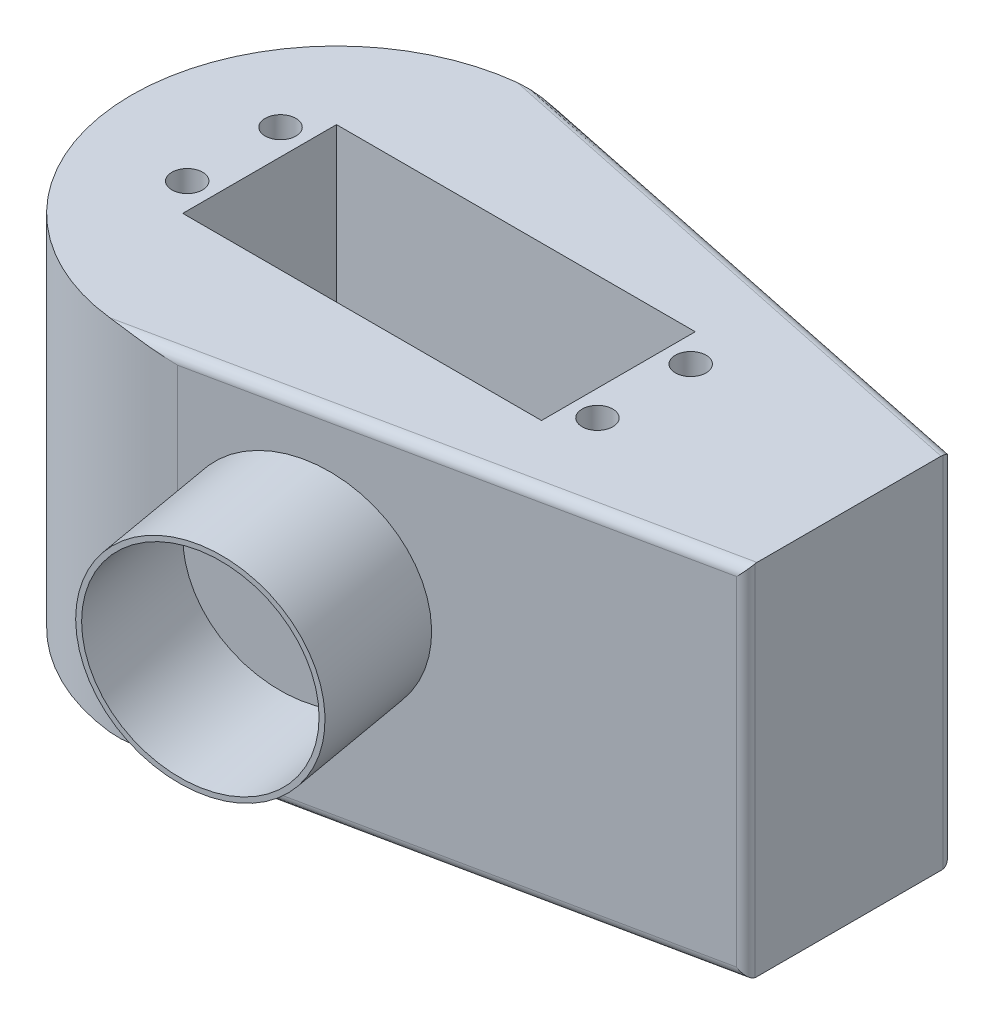
SolidWorks part; units mm, degrees
note: The reader was unsure of these and kept them because the rebuilt part matched: shared geometry of "Sketch3<3>".
material "ABS"
ref_plane "Front Plane" through (0, 0, 0) normal (0, 0, 1) x (1, 0, 0)
ref_plane "Top Plane" through (0, 0, 0) normal (0, 1, 0) x (1, 0, 0)
ref_plane "Right Plane" through (0, 0, 0) normal (1, 0, 0) x (0, 0, -1)
sketch "Sketch1" plane through (0, 0, 0) normal (0, 1, 0) x (1, 0, 0)
  line L0 (0, 0) -> (50, 0) construction
  line L1 (50, 10) -> (50, -10)
  line L2 (4.0843, 19.5785) -> (50, 10)
  line L3 (50, -10) -> (4.0843, -19.5785)
  arc A0 (4.0843, 19.5785) -> (4.0843, -19.5785) centre (0, 0) ccw
  point P3 (50, 0)
  dimension "D1" = 20
  dimension "D2" = 50
  dimension "D3" = 20
extrude "Boss-Extrude1" add sketch "Sketch1" along normal blind 35
sketch "Sketch2" plane through (0, 35, 0) normal (0, 1, 0) x (1, 0, 0)
  line L0 (0, 0) -> (-7.5, 0) construction
  line L1 (-7.5, 7.5) -> (27.5, 7.5)
  line L2 (-7.5, 7.5) -> (-7.5, -7.5)
  line L3 (-7.5, -7.5) -> (27.5, -7.5)
  line L4 (27.5, 7.5) -> (27.5, -7.5)
  dimension "D1" = 15
  dimension "D2" = 35
  dimension "D3" = 7.5
extrude "Cut-Extrude1" cut sketch "Sketch2" against normal blind 15
fillet "Fillet1" radius 1 6 edges at (50, 17.5, -10) (27.0421, 35, -14.7893) (27.0421, 0, -14.7893) (27.0421, 35, 14.7893) (50, 17.5, 10) (27.0421, 0, 14.7893)
sketch "Sketch3" plane through (0, 0, 0) normal (0, -1, 0) x (1, 0, 0)
  circle A0 centre (0, 0) radius 7.5
  circle A1 centre (0, 0) radius 3
  dimension "D1" = 15
  dimension "D2" = 6
extrude "Cut-Extrude2" cut sketch "Sketch3" against normal blind 10 contours A1 | A0 A1
extrude "Cut-Extrude3" cut sketch "Sketch3<3>" against normal through all contours A1
sketch "Sketch3<3>" plane through (0, 0, 0) normal (0, -1, 0) x (1, 0, 0) same geometry as "Sketch3"
ref_plane "Plane2" through (2.1118, 0, 11.9766) normal (-0.1736, 0, -0.9848) x (0, 1, 0)
ref_plane "Plane1" through (0, 0, -27.5) normal (0, 0, 1) x (1, 0, 0)
sketch "Sketch4" plane through (2.1118, 0, 11.9766) normal (-0.1736, 0, -0.9848) x (0, 1, 0)
  circle A0 centre (19.5911, 11.0539) radius 10
  dimension "D1" = 20
  dimension "D2" = 19.5911
  dimension "D3" = 11.0539
extrude "Extrude-Thin1" add sketch "Sketch4" against normal blind 20 thin
sketch "Sketch6" plane through (0, 35, 0) normal (0, 1, 0) x (1, 0, 0)
  line L0 (-7.5, 7.5) -> (-7.5, -7.5) construction
  line L2 (27.5, 7.5) -> (-7.5, 7.5) construction
  line L3 (10, 7.5) -> (10, -7.5) construction
  line L4 (-7.5, -7.5) -> (27.5, -7.5) construction
  line L5 (-19.8375, 0) -> (19.8375, 0) construction
  circle A0 centre (-10.01, 4.55) radius 1.5
  circle A1 centre (-10.01, -4.55) radius 1.5
  circle A2 centre (30.01, -4.55) radius 1.5
  circle A3 centre (30.01, 4.55) radius 1.5
  dimension "D1" = 3
  dimension "D2" = 2.51
  dimension "D3" = 2.95
extrude "Cut-Extrude4" cut sketch "Sketch6" against normal blind 8.2
mirror "Mirror1" [suppressed] about plane through (0, 0, -27.5) normal (0, 0, 1)
delete or keep bodies "Body-Delete/Keep 1" [suppressed] type delete bodies bodies 112
